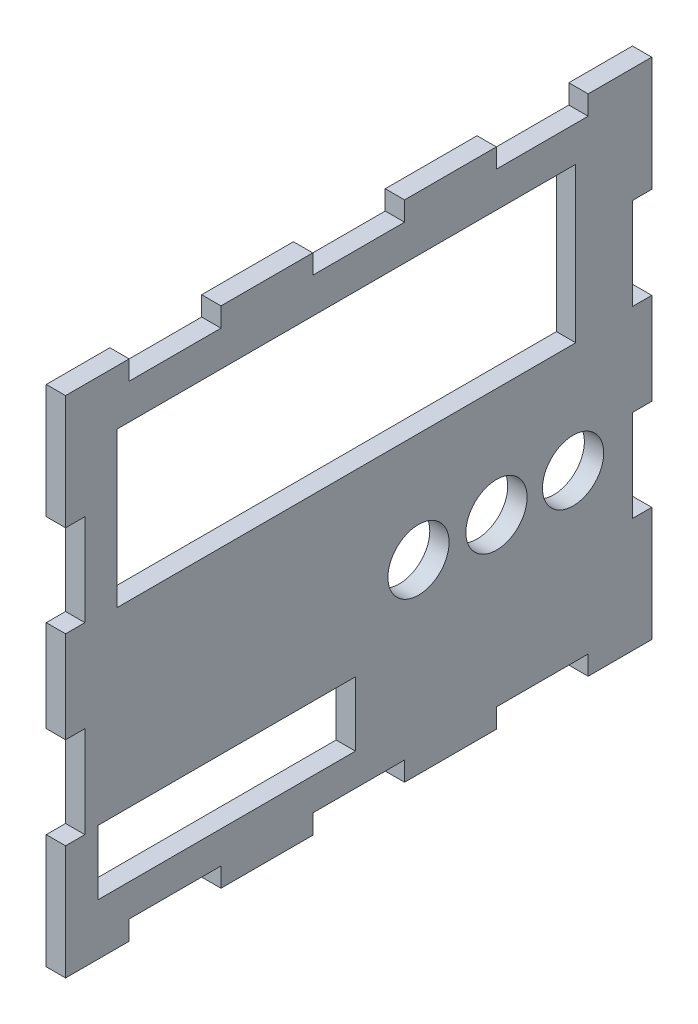
SolidWorks part; units mm, degrees
ref_plane "Front Plane" through (0, 0, 0) normal (0, 0, 1) x (1, 0, 0)
ref_plane "Top Plane" through (0, 0, 0) normal (0, 1, 0) x (1, 0, 0)
ref_plane "Right Plane" through (0, 0, 0) normal (1, 0, 0) x (0, 0, -1)
sketch "Sketch1" plane through (0, 0, 0) normal (1, 0, 0) x (0, 0, -1)
  line L148 (-46.8005, 37.0693) -> (-46.8005, 19.2943)
  line L149 (-46.8005, 19.2943) -> (-43.8005, 19.2943)
  line L150 (-43.8005, 19.2943) -> (-43.8005, 5.0443)
  line L151 (-43.8005, 5.0443) -> (-46.8005, 5.0443)
  line L152 (-46.8005, 5.0443) -> (-46.8005, -9.2057)
  line L153 (-46.8005, -9.2057) -> (-43.8005, -9.2057)
  line L154 (-43.8005, -9.2057) -> (-43.8005, -23.4557)
  line L155 (-43.8005, -23.4557) -> (-46.8005, -23.4557)
  line L156 (-46.8005, -23.4557) -> (-46.8005, -37.7057)
  line L157 (-46.8005, -37.7057) -> (-46.8005, -41.2307)
  line L158 (-46.8005, -41.2307) -> (-36.9255, -41.2307)
  line L159 (-36.9255, -41.2307) -> (-36.9255, -38.2307)
  line L160 (-36.9255, -38.2307) -> (-22.6755, -38.2307)
  line L161 (-22.6755, -38.2307) -> (-22.6755, -41.2307)
  line L162 (-22.6755, -41.2307) -> (-8.4255, -41.2307)
  line L163 (-8.4255, -41.2307) -> (-8.4255, -38.2307)
  line L164 (-8.4255, -38.2307) -> (5.8245, -38.2307)
  line L165 (5.8245, -38.2307) -> (5.8245, -41.2307)
  line L166 (5.8245, -41.2307) -> (20.0745, -41.2307)
  line L167 (20.0745, -41.2307) -> (20.0745, -38.2307)
  line L168 (20.0745, -38.2307) -> (34.3245, -38.2307)
  line L169 (34.3245, -38.2307) -> (34.3245, -41.2307)
  line L170 (34.3245, -41.2307) -> (44.1995, -41.2307)
  line L171 (44.1995, -41.2307) -> (44.1995, -23.4557)
  line L172 (44.1995, -23.4557) -> (41.1995, -23.4557)
  line L173 (41.1995, -23.4557) -> (41.1995, -9.2057)
  line L174 (41.1995, -9.2057) -> (44.1995, -9.2057)
  line L175 (44.1995, -9.2057) -> (44.1995, 5.0443)
  line L176 (44.1995, 5.0443) -> (41.1995, 5.0443)
  line L177 (41.1995, 5.0443) -> (41.1995, 19.2943)
  line L178 (41.1995, 19.2943) -> (44.1995, 19.2943)
  line L179 (44.1995, 19.2943) -> (44.1995, 33.5443)
  line L180 (44.1995, 33.5443) -> (44.1995, 37.0693)
  line L181 (44.1995, 37.0693) -> (34.3245, 37.0693)
  line L182 (34.3245, 37.0693) -> (34.3245, 34.0693)
  line L183 (34.3245, 34.0693) -> (20.0745, 34.0693)
  line L184 (20.0745, 34.0693) -> (20.0745, 37.0693)
  line L185 (20.0745, 37.0693) -> (5.8245, 37.0693)
  line L186 (5.8245, 37.0693) -> (5.8245, 34.0693)
  line L187 (5.8245, 34.0693) -> (-8.4255, 34.0693)
  line L188 (-8.4255, 34.0693) -> (-8.4255, 37.0693)
  line L189 (-8.4255, 37.0693) -> (-22.6755, 37.0693)
  line L190 (-22.6755, 37.0693) -> (-22.6755, 34.0693)
  line L191 (-22.6755, 34.0693) -> (-36.9255, 34.0693)
  line L192 (-36.9255, 34.0693) -> (-36.9255, 37.0693)
  line L193 (-36.9255, 37.0693) -> (-46.8005, 37.0693)
extrude "Boss-Extrude1" add sketch "Sketch1" along normal blind 3
sketch "Sketch2" plane through (3, 0, 0) normal (1, 0, 0) x (0, 0, -1)
  line L1 (-38.8005, 28.5693) -> (32.3995, 28.5693)
  line L2 (-38.8005, 28.5693) -> (-38.8005, 4.5693)
  line L3 (-38.8005, 4.5693) -> (32.3995, 4.5693)
  line L4 (32.3995, 28.5693) -> (32.3995, 4.5693)
  line L12 (41.1995, -23.4557) -> (41.1995, -9.2057) construction
  line L13 (-41.8005, -23.2307) -> (-1.8005, -23.2307)
  line L14 (-41.8005, -23.2307) -> (-41.8005, -33.2307)
  line L15 (-41.8005, -33.2307) -> (-1.8005, -33.2307)
  line L16 (-1.8005, -23.2307) -> (-1.8005, -33.2307)
  line L17 (-43.8005, -9.2057) -> (-43.8005, -23.4557) construction
  line L18 (-36.9255, -38.2307) -> (-22.6755, -38.2307) construction
  line L19 (2.1995, -6.8492) -> (37.9891, -6.8492) construction
  line L20 (2.1995, -6.8492) -> (2.1995, -17.9622) construction
  line L21 (-43.8005, 19.2943) -> (-43.8005, 5.0443) construction
  line L22 (34.3245, 34.0693) -> (20.0745, 34.0693) construction
  line L23 (2.1995, -17.9622) -> (37.9891, -17.9622) construction
  line L24 (37.9891, -6.8492) -> (37.9891, -17.9622) construction
  line L25 (41.1995, -9.2057) -> (44.1995, -9.2057) construction
  line L26 (31.9891, -12.4057) -> (7.9891, -12.4057) construction
  circle A3 centre (20.0943, -12.4057) radius 4.75
  circle A4 centre (7.9891, -12.4057) radius 4.75
  circle A5 centre (31.9891, -12.4057) radius 4.75
  point P26 (20.0943, -6.8492)
  point P27 (20.0943, -17.9622)
  point P33 (37.9891, -12.4057)
  dimension "D4" = 39
  dimension "D6" = 9.5
  dimension "D13" = 9.5
  dimension "D14" = 9.5
  dimension "D2" = 42
  dimension "D3" = 15
  dimension "D5" = 3.2
  dimension "D7" = 40
  dimension "D8" = 5
  dimension "D9" = 10
  dimension "D10" = 24
  dimension "D11" = 71.2
  dimension "D12" = 5.5
extrude "Cut-Extrude1" cut sketch "Sketch2" against normal blind 3
